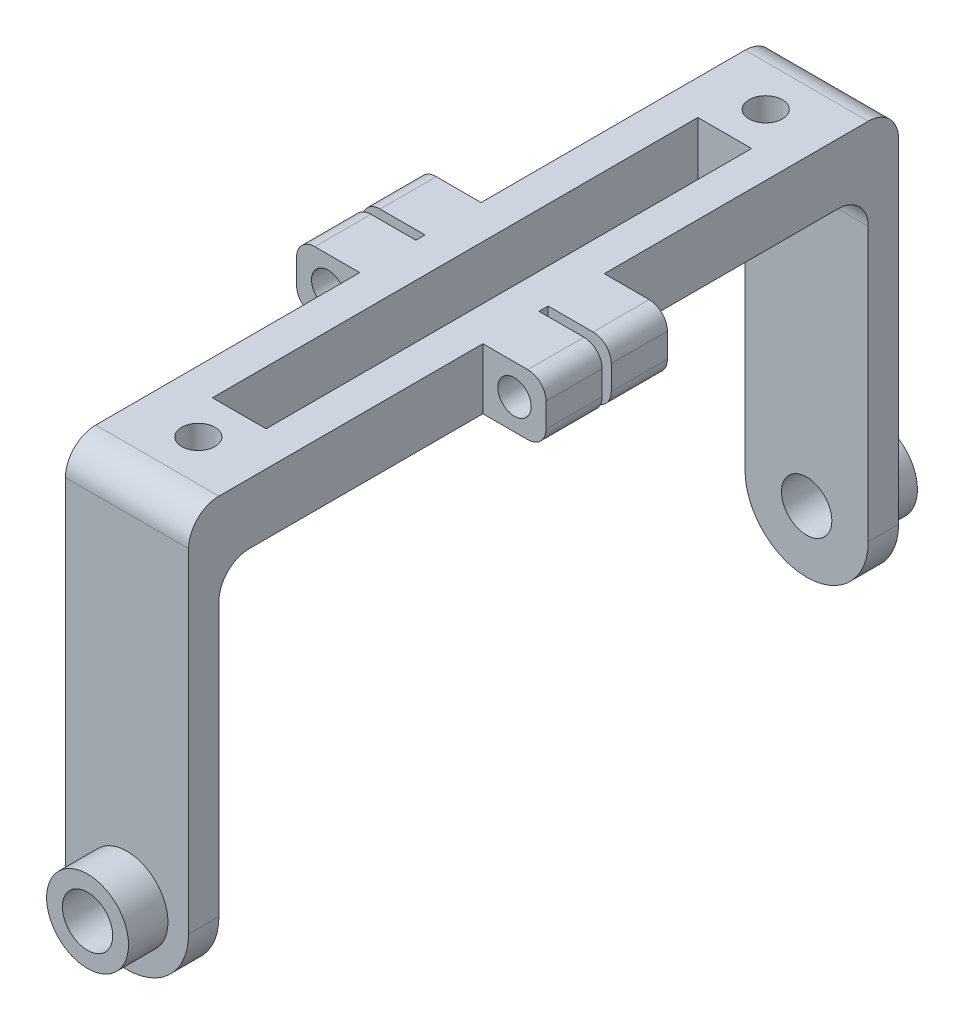
SolidWorks part; units mm, degrees
ref_plane "Front Plane" through (0, 0, 0) normal (0, 0, 1) x (1, 0, 0)
ref_plane "Top Plane" through (0, 0, 0) normal (0, 1, 0) x (1, 0, 0)
ref_plane "Right Plane" through (0, 0, 0) normal (1, 0, 0) x (0, 0, -1)
sketch "Sketch1" plane through (0, 0, 0) normal (0, 0, 1) x (1, 0, 0)
  circle A0 centre (-52, 0) radius 7.15
  circle A1 centre (-52, 0) radius 4.15
  dimension "D1" = 14.3
  dimension "D2" = 8.3
extrude "Boss-Extrude1" add sketch "Sketch1" against normal up to surface (5 mm away)
sketch "Sketch2" plane through (0, 0, -125) normal (0, 0, 1) x (1, 0, 0)
  circle A0 centre (-52, 0) radius 4.15 construction
  circle A1 centre (-52, 0) radius 7.15
  circle A2 centre (-52, 0) radius 7.15
  circle A3 centre (-52, 0) radius 4.15
  dimension "D1" = 0
extrude "Boss-Extrude2" add sketch "Sketch2" against normal up to surface (5 mm away) separate body
sketch "Sketch3" plane through (0, 0, -125) normal (0, 0, 1) x (1, 0, 0)
  circle A0 centre (-52, 0) radius 7.15 construction
  circle A1 centre (-52, 0) radius 4.15 construction
  circle A2 centre (-52, 0) radius 7.15
  circle A3 centre (-52, 0) radius 4.15
extrude "Boss-Extrude3" add sketch "Sketch3" along normal blind 1.5
sketch "Sketch4" plane through (0, 0, -5) normal (0, 0, -1) x (-1, 0, 0)
  circle A0 centre (52, 0) radius 4.15 construction
  circle A1 centre (52, 0) radius 7.15 construction
  circle A2 centre (52, 0) radius 4.15
  circle A3 centre (52, 0) radius 7.15
extrude "Boss-Extrude4" add sketch "Sketch4" along normal blind 1.5
sketch "Sketch5" plane through (0, 0, -6.5) normal (0, 0, -1) x (-1, 0, 0)
  line L0 (59.15, 0) -> (62.15, 0)
  line L1 (44.85, 0) -> (41.85, 0)
  line L2 (41.85, 0) -> (41.85, 40)
  line L3 (62.15, 0) -> (62.15, 40)
  line L4 (41.85, 40) -> (62.15, 40)
  circle A0 centre (52, 0) radius 7.15 construction
  circle A1 centre (52, 0) radius 10.15
  circle A2 centre (52, 0) radius 4.15
  circle M6 centre (52, 0) radius 7.15
  circle M7 centre (52, 0) radius 4.15
  dimension "D1" = 3
  dimension "D2" = 3
  dimension "D3" = 40
  dimension "D4" = 40
extrude "Boss-Extrude5" add sketch "Sketch5" along normal blind 5 contours M6 M7 | L1 A1 L0 M6 | L0 A1 L1 M6 | A1 L3 L4 L2 region at (-52, 7.377, -6.5) region at (-52, -6.9478, -6.5) region at (-60.65, -0.227, -6.5) region at (-52, 23.9058, -6.5)
sketch "Sketch6" plane through (0, 0, -123.5) normal (0, 0, 1) x (1, 0, 0)
  line L3 (-62.15, 40) -> (-62.15, 0)
  line L4 (-41.85, 40) -> (-62.15, 40)
  line L5 (-41.85, 0) -> (-41.85, 40)
  line L6 (-62.15, 40) -> (-62.15, 0)
  line L7 (-41.85, 40) -> (-62.15, 40)
  line L8 (-41.85, 0) -> (-41.85, 40)
  circle A0 centre (-52, 0) radius 4.15 construction
  arc A1 (-62.15, 0) -> (-41.85, 0) centre (-52, 0) ccw
  arc A2 (-62.15, 0) -> (-41.85, 0) centre (-52, 0) ccw
  circle A3 centre (-52, 0) radius 4.15
  dimension "D1" = 0
extrude "Boss-Extrude6" add sketch "Sketch6" along normal blind 5
sketch "Sketch7" plane through (0, 0, -118.5) normal (0, 0, 1) x (1, 0, 0)
  line L0 (-41.85, 0) -> (-41.85, 40) construction
  line L1 (-62.15, 40) -> (-41.85, 40)
  line L2 (-62.15, 40) -> (-62.15, 30)
  line L3 (-62.15, 30) -> (-41.85, 30)
  line L4 (-41.85, 40) -> (-41.85, 30)
  dimension "D1" = 10
extrude "Boss-Extrude7" add sketch "Sketch7" along normal up to surface (107 mm away) up to face at (-52, 17.4625, -11.5)
sketch "Sketch8" plane through (0, 40, 0) normal (0, 1, 0) x (1, 0, 0)
  circle A1 centre (-52, 65) radius 4.15
  dimension "D1" = 8.3
extrude "Cut-Extrude1" cut sketch "Sketch8" against normal through all
fillet "Fillet1" radius 5 4 edges at (-52, 40, -6.5) (-52, 40, -123.5) (-52, 30, -118.5) (-52, 30, -11.5)
sketch "Sketch10" plane through (0, 40, 0) normal (0, 1, 0) x (1, 0, 0)
  line L0 (-56.225, 25) -> (-56.225, 105)
  line L1 (-56.225, 105) -> (-47.775, 105)
  line L2 (-47.775, 105) -> (-47.775, 25)
  line L3 (-52, 65) -> (-54.2764, 65)
  line L4 (-56.225, 25) -> (-47.775, 25)
  circle A0 centre (-52, 65) radius 4.225
  point P9 (-47.775, 65)
  point P10 (-56.225, 65)
  dimension "D1" = 8.45
  dimension "D2" = 40
extrude "Cut-Extrude3" cut sketch "Sketch10" against normal blind 18.9 contours A0 L0 L4 L2 | A0 L2 L1 L0 | A0 region at (-52, 40, -43.353) region at (-52, 40, -86.647)
sketch "Sketch11" plane through (0, 0, 0) normal (0, 0, 1) x (1, 0, 0)
  circle A0 centre (-52, 0) radius 6.75
  circle A1 centre (-52, 0) radius 7.15
  dimension "D1" = 13.5
extrude "Cut-Extrude4" cut sketch "Sketch11" against normal up to surface (6.5 mm away) up to face at (-59.15, 0, -6.5)
sketch "Sketch12" plane through (0, 0, -130) normal (0, 0, -1) x (-1, 0, 0)
  circle A0 centre (52, 0) radius 7.15 construction
  circle A1 centre (52, 0) radius 7.15
  circle A2 centre (52, 0) radius 6.75 construction
  circle A3 centre (52, 0) radius 6.75
extrude "Cut-Extrude5" cut sketch "Sketch12" against normal up to surface (6.5 mm away) up to face at (-44.85, 0, -123.5)
sketch "Sketch13" plane through (0, 40, 0) normal (0, 1, 0) x (1, 0, 0)
  line L0 (-52, 11.5) -> (-52, 25)
  line L1 (-62.15, 11.5) -> (-41.85, 11.5) construction
  line L2 (-56.225, 25) -> (-47.775, 25) construction
  line L3 (-52, 105) -> (-52, 118.5)
  line L4 (-56.225, 105) -> (-47.775, 105) construction
  line L5 (-41.85, 118.5) -> (-62.15, 118.5) construction
  circle A0 centre (-52, 18.25) radius 2.75
  circle A1 centre (-52, 111.75) radius 2.75
  dimension "D1" = 5.5
  dimension "D2" = 5.5
extrude "Cut-Extrude6" cut sketch "Sketch13" against normal blind 18.9 contours L0 A0 | L3 A1 | L3 A1 | A0 region at (-53.1671, 40, -18.25) region at (-53.1671, 40, -111.75) region at (-50.8329, 40, -111.75)
sketch "Sketch14" plane through (-41.85, 0, 0) normal (1, 0, 0) x (0, 0, -1)
  line L0 (65, 30) -> (65, 40)
  line L2 (118.5, 40) -> (11.5, 40) construction
  line L3 (65.75, 30) -> (65.75, 40)
  line L4 (16.5, 30) -> (113.5, 30) construction
  line L5 (64.25, 30) -> (64.25, 40)
  line L6 (75, 30) -> (75, 40)
  line L7 (55, 30) -> (55, 40)
  line L8 (55, 40) -> (75, 40)
  line L9 (75, 30) -> (55, 30)
  line M2 (118.5, 40) -> (11.5, 40)
  line M8 (16.5, 30) -> (113.5, 30)
  dimension "D1" = 0.75
  dimension "D2" = 0.75
  dimension "D3" = 10
  dimension "D4" = 10
extrude "Boss-Extrude8" add sketch "Sketch14" along normal blind 0.4 contours L7 L5 M8 M2 | L6 L3 M8 M2 region at (-41.85, 35, -70.375) region at (-41.85, 35, -59.625)
sketch "Sketch15" plane through (-62.15, 0, 0) normal (-1, 0, 0) x (0, 0, 1)
  line L0 (-55, 40) -> (-55, 30) construction
  line L1 (-55, 30) -> (-64.25, 30) construction
  line L2 (-64.25, 30) -> (-64.25, 40) construction
  line L3 (-64.25, 40) -> (-55, 40) construction
  line L4 (-65.75, 30) -> (-75, 30) construction
  line L5 (-75, 30) -> (-75, 40) construction
  line L6 (-75, 40) -> (-65.75, 40) construction
  line L7 (-65.75, 40) -> (-65.75, 30) construction
  line L8 (-55, 40) -> (-55, 30)
  line L9 (-55, 30) -> (-64.25, 30)
  line L10 (-64.25, 30) -> (-64.25, 40)
  line L11 (-64.25, 40) -> (-55, 40)
  line L12 (-65.75, 30) -> (-75, 30)
  line L13 (-75, 30) -> (-75, 40)
  line L14 (-75, 40) -> (-65.75, 40)
  line L15 (-65.75, 40) -> (-65.75, 30)
extrude "Boss-Extrude9" add sketch "Sketch15" along normal blind 0.4
sketch "Sketch17" plane through (-41.45, 0, 0) normal (1, 0, 0) x (0, 0, -1)
  line L4 (55, 40) -> (55, 30)
  line L5 (55, 30) -> (64.25, 30)
  line L6 (64.25, 30) -> (64.25, 40)
  line L7 (64.25, 40) -> (55, 40)
  line L8 (55, 40) -> (55, 30)
  line L9 (55, 30) -> (64.25, 30)
  line L10 (64.25, 30) -> (64.25, 40)
  line L11 (64.25, 40) -> (55, 40)
  line L12 (65.75, 30) -> (75, 30)
  line L13 (75, 30) -> (75, 40)
  line L14 (75, 40) -> (65.75, 40)
  line L15 (65.75, 40) -> (65.75, 30)
  line L16 (65.75, 30) -> (75, 30)
  line L17 (75, 30) -> (75, 40)
  line L18 (75, 40) -> (65.75, 40)
  line L19 (65.75, 40) -> (65.75, 30)
  dimension "D1" = 0
  dimension "D2" = 0
extrude "Boss-Extrude10" add sketch "Sketch17" along normal blind 10
sketch "Sketch18" plane through (0, 0, -75) normal (0, 0, -1) x (-1, 0, 0)
  line L0 (31.45, 35) -> (41.85, 35)
  line L1 (31.45, 30) -> (31.45, 40) construction
  circle A0 centre (36.65, 35) radius 2.75
  dimension "D1" = 5.5
extrude "Cut-Extrude7" cut sketch "Sketch18" against normal blind 26 contours L0 A0 | L0 A0 region at (-36.65, 36.1671, -75) region at (-36.65, 33.8329, -75)
sketch "Sketch20" plane through (-62.55, 0, 0) normal (-1, 0, 0) x (0, 0, 1)
  line L4 (-65.75, 30) -> (-65.75, 40)
  line L5 (-65.75, 40) -> (-75, 40)
  line L6 (-75, 40) -> (-75, 30)
  line L7 (-75, 30) -> (-65.75, 30)
  line L8 (-65.75, 30) -> (-65.75, 40)
  line L9 (-65.75, 40) -> (-75, 40)
  line L10 (-75, 40) -> (-75, 30)
  line L11 (-75, 30) -> (-65.75, 30)
  line L12 (-55, 40) -> (-64.25, 40)
  line L13 (-64.25, 40) -> (-64.25, 30)
  line L14 (-64.25, 30) -> (-55, 30)
  line L15 (-55, 30) -> (-55, 40)
  line L16 (-55, 40) -> (-64.25, 40)
  line L17 (-64.25, 40) -> (-64.25, 30)
  line L18 (-64.25, 30) -> (-55, 30)
  line L19 (-55, 30) -> (-55, 40)
  dimension "D1" = 0
  dimension "D2" = 0
extrude "Boss-Extrude11" add sketch "Sketch20" along normal blind 10
sketch "Sketch21" plane through (0, 0, -75) normal (0, 0, -1) x (-1, 0, 0)
  line L0 (72.55, 35) -> (62.15, 35)
  line L1 (72.55, 40) -> (72.55, 30) construction
  circle A0 centre (67.35, 35) radius 2.75
  dimension "D1" = 5.5
extrude "Cut-Extrude8" cut sketch "Sketch21" against normal through all both and the other way through all contours L0 A0 | A0 region at (-67.35, 36.1671, -75)
fillet "Fillet2" radius 3 8 edges at (-72.55, 30, -70.375) (-72.55, 40, -70.375) (-72.55, 30, -59.625) (-72.55, 40, -59.625) (-31.45, 30, -70.375) (-31.45, 30, -59.625) (-31.45, 40, -59.625) (-31.45, 40, -70.375)
sketch "Sketch23" plane through (-41.85, 0, 0) normal (1, 0, 0) x (0, 0, -1)
  line L0 (6.5, 17.5) -> (123.5, 17.5)
  line L1 (6.5, 0) -> (6.5, 35) construction
  line L2 (123.5, 0) -> (123.5, 35) construction
  line L3 (123.5, 17.5) -> (123.5, 19.5)
  line L4 (123.5, 19.5) -> (6.5, 19.5)
  line L5 (6.5, 19.5) -> (6.5, 17.5)
  dimension "D1" = 2
extrude "Cut-Extrude9" cut sketch "Sketch23" against normal blind 37
move or copy body "Body-Move/Copy1" bodies to move or copy 119 copy no translate (0, 20, 0)
sketch "Sketch24" plane through (0, 17.5, 0) normal (0, 1, 0) x (1, 0, 0)
  line L0 (-62.15, 6.5) -> (-41.85, 6.5) construction
  line L1 (-41.85, 6.5) -> (-41.85, 11.5) construction
  line L2 (-41.85, 11.5) -> (-62.15, 11.5) construction
  line L3 (-62.15, 11.5) -> (-62.15, 6.5) construction
  line L4 (-62.15, 118.5) -> (-41.85, 118.5) construction
  line L5 (-41.85, 118.5) -> (-41.85, 123.5) construction
  line L6 (-41.85, 123.5) -> (-62.15, 123.5) construction
  line L7 (-62.15, 123.5) -> (-62.15, 118.5) construction
  line L8 (-62.15, 6.5) -> (-41.85, 6.5)
  line L9 (-41.85, 6.5) -> (-41.85, 11.5)
  line L10 (-41.85, 11.5) -> (-62.15, 11.5)
  line L11 (-62.15, 11.5) -> (-62.15, 6.5)
  line L12 (-62.15, 118.5) -> (-41.85, 118.5)
  line L13 (-41.85, 118.5) -> (-41.85, 123.5)
  line L14 (-41.85, 123.5) -> (-62.15, 123.5)
  line L15 (-62.15, 123.5) -> (-62.15, 118.5)
extrude "Boss-Extrude12" add sketch "Sketch24" along normal up to surface (22 mm away) up to face at (-52, 39.5, -9)
sketch "Sketch25" plane through (-56.225, 0, 0) normal (1, 0, 0) x (0, 0, -1)
  line L4 (25, 50) -> (105, 50)
  line L5 (105, 50) -> (105, 60)
  line L6 (105, 60) -> (25, 60)
  line L7 (25, 60) -> (25, 50)
  line L8 (25, 50) -> (105, 50)
  line L9 (105, 50) -> (105, 60)
  line L10 (105, 60) -> (25, 60)
  line L11 (25, 60) -> (25, 50)
  dimension "D1" = 0
extrude "Cut-Extrude10" cut sketch "Sketch25" against normal blind 0.2
sketch "Sketch26" plane through (-47.775, 0, 0) normal (-1, 0, 0) x (0, 0, 1)
  line L4 (-105, 50) -> (-25, 50)
  line L5 (-25, 50) -> (-25, 60)
  line L6 (-25, 60) -> (-105, 60)
  line L7 (-105, 60) -> (-105, 50)
  line L8 (-105, 50) -> (-25, 50)
  line L9 (-25, 50) -> (-25, 60)
  line L10 (-25, 60) -> (-105, 60)
  line L11 (-105, 60) -> (-105, 50)
  dimension "D1" = 0
extrude "Cut-Extrude11" cut sketch "Sketch26" against normal blind 0.2
